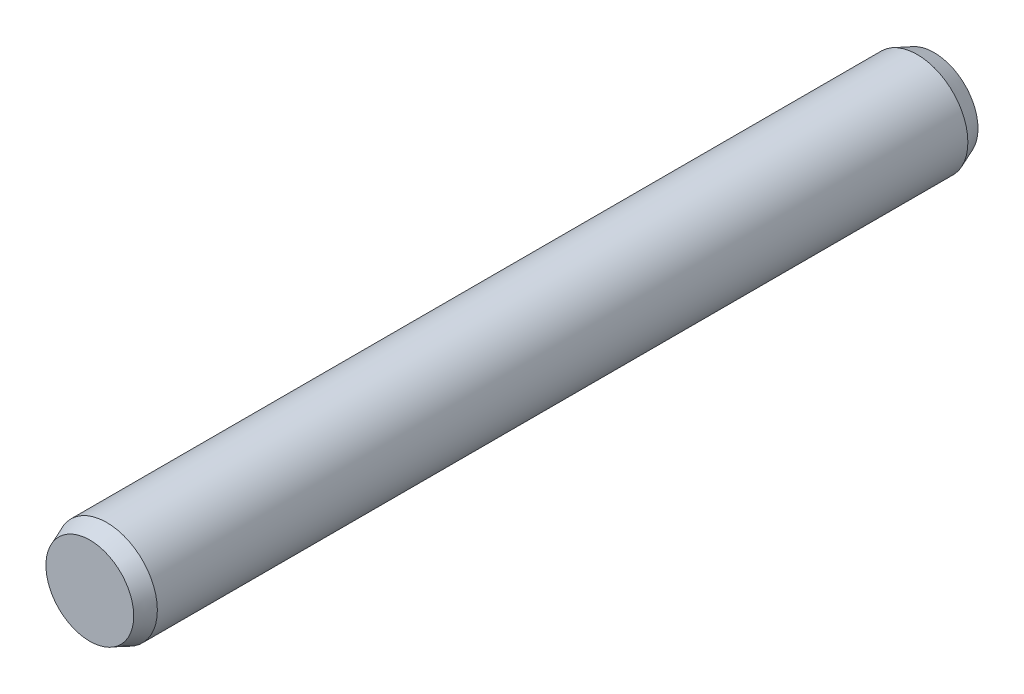
SolidWorks part; units mm, degrees
ref_plane "Front Plane" through (0, 0, 0) normal (0, 0, 1) x (1, 0, 0)
ref_plane "Top Plane" through (0, 0, 0) normal (0, 1, 0) x (1, 0, 0)
ref_plane "Right Plane" through (0, 0, 0) normal (1, 0, 0) x (0, 0, -1)
sketch "Sketch1" plane through (0, 0, 0) normal (0, 0, 1) x (1, 0, 0)
  circle A0 centre (0, 0) radius 1.5
  dimension "D1" = 3
extrude "Boss-Extrude1" add sketch "Sketch1" along normal mid plane 25
chamfer "Chamfer1" distance 0.5 distance2 0.2 1 edges at (1.5, 0, 12.5) first distance on face at (1.5, 0, 12.5)
chamfer "Chamfer2" distance 0.2 distance2 0.5 1 edges at (1.5, 0, -12.5) first distance on face at (1.5, 0, -12.5)
